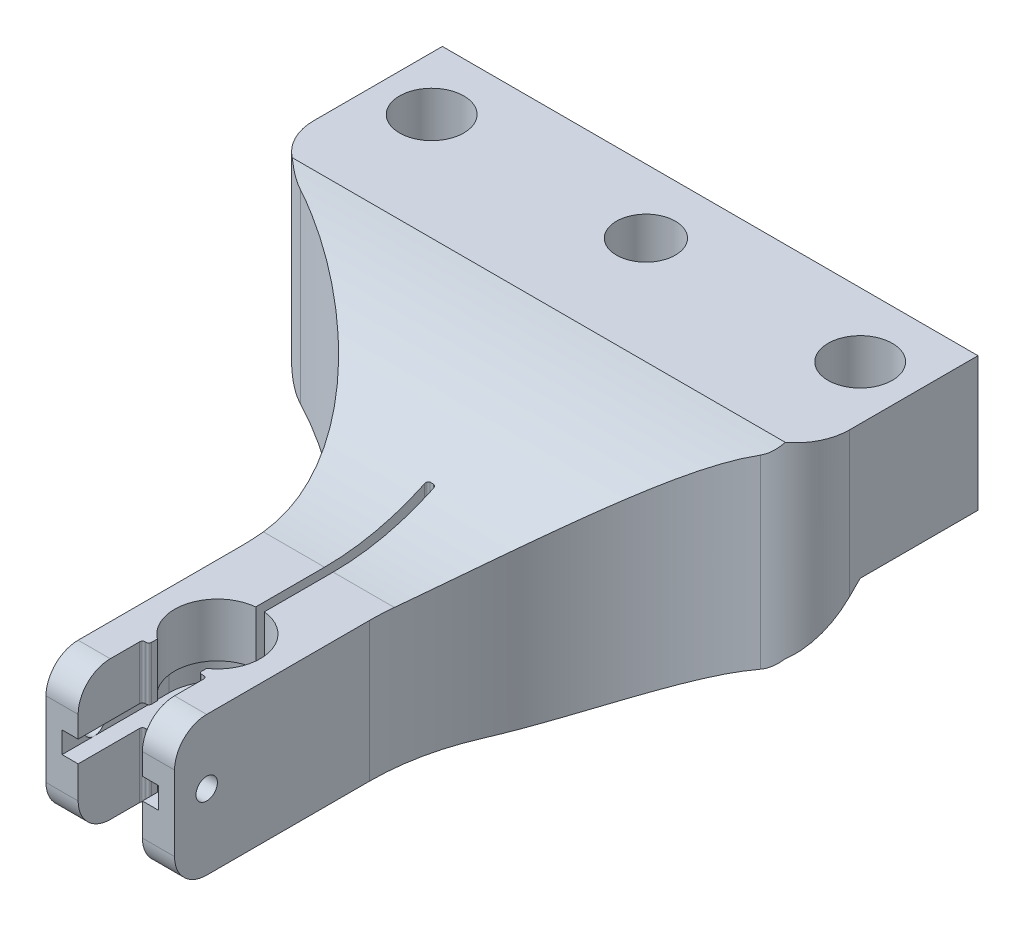
SolidWorks part; units mm, degrees
ref_plane "Front Plane" through (0, 0, 0) normal (0, 0, 1) x (1, 0, 0)
ref_plane "Top Plane" through (0, 0, 0) normal (0, 1, 0) x (1, 0, 0)
ref_plane "Right Plane" through (0, 0, 0) normal (1, 0, 0) x (0, 0, -1)
sketch "Sketch1" plane through (0, 0, 0) normal (0, 1, 0) x (1, 0, 0)
  line L0 (0, 0) -> (0, 40) construction
  line L1 (-20, 40) -> (20, 40) construction
  line L3 (-25, 46) -> (-25, 30)
  line L6 (-25, 46) -> (25, 46)
  line L7 (25, 46) -> (25, 30)
  line L11 (6, 30) -> (25, 30)
  line L12 (-6, 30) -> (-25, 30)
  line L13 (6, 30) -> (6, -10)
  line L14 (6, -10) -> (-6, -10)
  line L15 (-6, -10) -> (-6, 30)
  line L18 (0, 0) -> (0, -10) construction
  circle A1 centre (-20, 40) radius 3
  circle A2 centre (20, 40) radius 3
  circle A3 centre (0, 40) radius 2.75
  point P12 (0, 46)
  point P22 (0, -10)
  dimension "D3" = 10
  dimension "D4" = 16
  dimension "D5" = 6
  dimension "D6" = 6
  dimension "D7" = 5.5
  dimension "D2" = 12
  dimension "D9" = 10
  dimension "D10" = 40
  dimension "D11" = 50
  dimension "D16" = 40
extrude "Boss-Extrude1" add sketch "Sketch1" along normal blind 25 contours L11 L7 L6 L3 L12 A3 A2 A1 region at (0, 0, -26.6633)
fillet "Fillet8" radius 22 2 edges at (6, 12.5, -30) (-6, 12.5, -30)
sketch "Sketch2" plane through (0, 0, 0) normal (0, 1, 0) x (1, 0, 0)
  circle A0 centre (0, 0) radius 4
  dimension "D1" = 8
extrude "Cut-Extrude1" cut sketch "Sketch2" along normal up to surface (25 mm away) up to face at (0, 25, -37.25)
sketch "Sketch4" plane through (0, 0, 0) normal (0, -1, 0) x (-1, 0, 0)
  circle A0 centre (0, 0) radius 4.5
  dimension "D1" = 9
extrude "Cut-Extrude2" cut sketch "Sketch4" against normal blind 2 from offset 6 offset against normal yes
sketch "Sketch5" plane through (0, 25, 0) normal (0, 1, 0) x (1, 0, 0)
  line L0 (0, 20) -> (0, -10) construction
  line L1 (0, 20) -> (-0.4, 20)
  line L2 (-0.4, 20) -> (-0.4, 0)
  line L3 (-0.4, 0) -> (-2.4, 0)
  line L5 (-3, -10) -> (3, -10)
  line L7 (2.2793, 0) -> (0.4, 0)
  line L8 (0.4, 0) -> (0.4, 20)
  line L9 (0.4, 20) -> (0, 20)
  line L10 (6, -10) -> (-6, -10) construction
  line L11 (-2.4, 0) -> (-2.4, -4)
  line L12 (-2.4, -4) -> (-3, -4)
  line L13 (-3, -4) -> (-3, -10)
  line L14 (2.2793, 0) -> (2.2793, -4)
  line L15 (2.2793, -4) -> (3, -4)
  line L16 (3, -4) -> (3, -10)
  line L17 (6, -10) -> (-6, -10) construction
  point P2 (0, -10)
  point P12 (-3, -7)
  point P22 (0, 0)
  point P23 (-3, -3.9787)
  point P24 (3, -3.9325)
  dimension "D1" = 4
  dimension "D2" = 0.4
  dimension "D3" = 3
  dimension "D4" = 2
  dimension "D5" = 20
extrude "Cut-Extrude3" cut sketch "Sketch5" against normal up to surface (25 mm away) up to face at (0, 0, 4)
fillet "Fillet13" radius 0.25 6 edges at (-2.4, 12.5, 4) (2.2793, 12.5, 4) (0.4, 12.5, -20) (-0.4, 12.5, -20) (3, 12.5, 4) (-3, 12.5, 4)
sketch "Sketch6" plane through (0, 0, 0) normal (0, 0, 1) x (1, 0, 0)
  line L1 (-4.5, 6) -> (4.5, 6)
  line L2 (-4.5, 6) -> (-4.5, 8)
  line L3 (-4.5, 8) -> (4.5, 8)
  line L4 (4.5, 6) -> (4.5, 8)
extrude "Cut-Extrude4" cut sketch "Sketch6" along normal blind 10
sketch "Sketch8" plane through (-6, 0, 0) normal (-1, 0, 0) x (0, 0, 1)
  line L1 (10, 0) -> (-8.2055, 0) construction
  line L2 (10, 25) -> (10, 0) construction
  circle A0 centre (7, 7) radius 1
  dimension "D1" = 2
  dimension "D2" = 3
  dimension "D3" = 7
extrude "Cut-Extrude5" cut sketch "Sketch8" against normal through all both and the other way through all
sketch "Sketch9" plane through (-25, 0, 0) normal (-1, 0, 0) x (0, 0, 1)
  line L0 (-30, 13) -> (10, 13)
  line L3 (10, 13) -> (10, 25)
  line L4 (10, 25) -> (-30, 25)
  line L5 (-30, 25) -> (-30, 13)
  dimension "D1" = 12
extrude "Cut-Extrude6" cut sketch "Sketch9" against normal up to surface (50 mm away) up to face at (25, 12.5, -38)
fillet "Fillet9" radius 22 1 edges at (0, 13, -30)
sketch "Sketch10" plane through (-25, 0, 0) normal (-1, 0, 0) x (0, 0, 1)
  line L0 (-30, 25) -> (-30, 0) construction
  line L1 (-46, 0) -> (-30, 0)
  line L2 (-46, 0) -> (-46, 12.5)
  line L3 (-46, 12.5) -> (-30, 12.5)
  line L4 (-30, 0) -> (-30, 12.5)
extrude "Cut-Extrude7" cut sketch "Sketch10" against normal up to surface (50 mm away) up to face at (25, 12.5, -38)
fillet "Fillet10" radius 5 1 edges at (0, 12.5, -30) profile chamfer
fillet "Fillet11" radius 15 1 edges at (0, 0, -30)
fillet "Fillet12" radius 5 2 edges at (25, 16.25, -30) (-25, 16.25, -30)
fillet "Fillet7" radius 3 4 edges at (-4.5, 0, 10) (4.5, 0, 10) (-4.5, 13, 10) (4.5, 13, 10)
sketch "Sketch12" plane through (0, -11.25, -11.25) normal (0, -0.7071, -0.7071) x (1, 0, 0)
  line L0 (0, -33.5876) -> (0, -26.5165) construction
  line L1 (25, -33.5876) -> (-25, -33.5876) construction
  line L2 (-23.0092, -26.5165) -> (23.0092, -26.5165) construction
  line L3 (-12.3319, -30.0228) -> (12.3319, -30.0228) construction
  text T0 "Jadhav Lab"
extrude "Boss-Extrude3" add sketch "Sketch12" along normal blind 0.5
